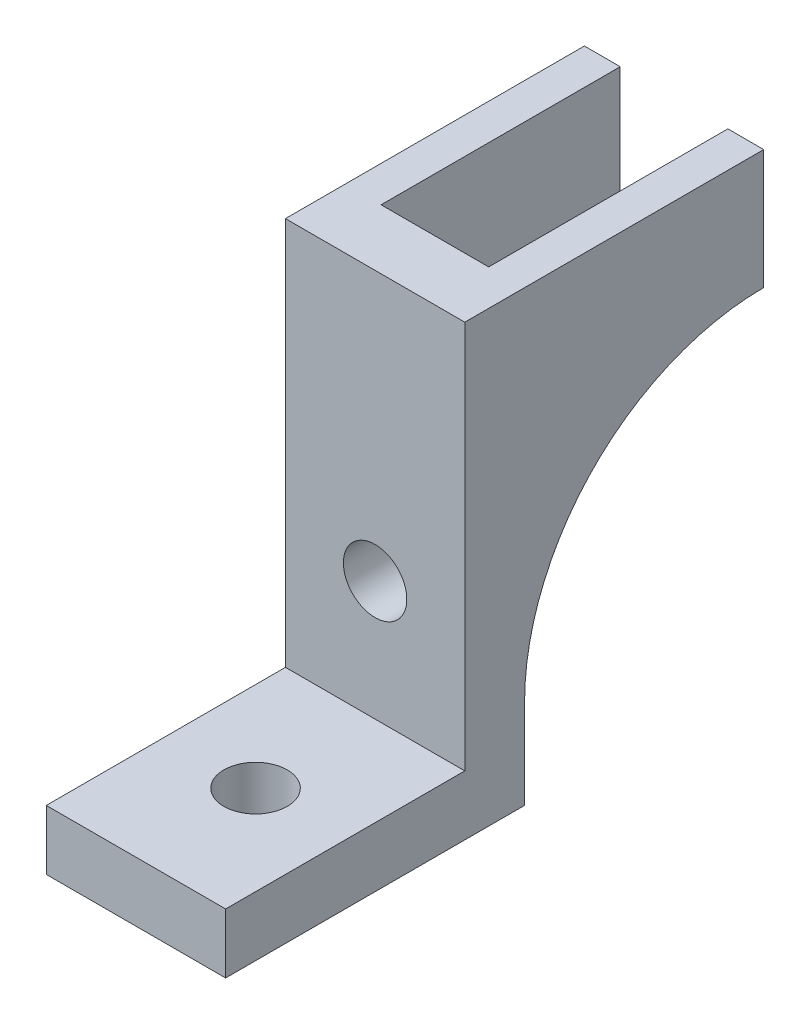
SolidWorks part; units mm, degrees
ref_plane "Front Plane" through (0, 0, 0) normal (0, 0, 1) x (1, 0, 0)
ref_plane "Top Plane" through (0, 0, 0) normal (0, 1, 0) x (1, 0, 0)
ref_plane "Right Plane" through (0, 0, 0) normal (1, 0, 0) x (0, 0, -1)
sketch "Sketch2" plane through (0, 0, 0) normal (0, 0, 1) x (1, 0, 0)
  line L1 (0, 0) -> (15, 0)
  line L2 (0, 0) -> (0, 37.5)
  line L3 (0, 37.5) -> (15, 37.5)
  line L4 (15, 0) -> (15, 37.5)
  dimension "D1" = 37.5
  dimension "D2" = 15
extrude "Boss-Extrude1" add sketch "Sketch2" along normal blind 5
sketch "Sketch3" plane through (0, 0, 5) normal (0, 0, 1) x (1, 0, 0)
  line L0 (15, 0) -> (15, 37.5) construction
  line L1 (0, 0) -> (15, 0)
  line L2 (0, 0) -> (0, 5)
  line L3 (0, 5) -> (15, 5)
  line L4 (15, 0) -> (15, 5)
  dimension "D1" = 5
extrude "Boss-Extrude2" add sketch "Sketch3" along normal blind 20
sketch "Sketch4" plane through (0, 0, 0) normal (0, 0, -1) x (-1, 0, 0)
  line L1 (-15, 37.5) -> (-12, 37.5)
  line L2 (-15, 37.5) -> (-15, 27.5)
  line L3 (-15, 27.5) -> (-12, 27.5)
  line L4 (-12, 37.5) -> (-12, 27.5)
  line L5 (0, 37.5) -> (-3, 37.5)
  line L6 (0, 37.5) -> (0, 27.5)
  line L7 (0, 27.5) -> (-3, 27.5)
  line L8 (-3, 37.5) -> (-3, 27.5)
  dimension "D1" = 3
  dimension "D2" = 3
  dimension "D3" = 10
  dimension "D4" = 10
extrude "Boss-Extrude3" add sketch "Sketch4" along normal blind 20
fillet "Fillet1" radius 20 2 edges at (1.5, 27.5, 0) (13.5, 27.5, 0)
sketch "Sketch6" plane through (0, 0, 0) normal (0, -1, 0) x (1, 0, 0)
  line L0 (0, 25) -> (15, 25) construction
  line L1 (0, 25) -> (0, 0) construction
  circle A0 centre (7.5, 15) radius 2.65
  dimension "D1" = 5.3
  dimension "D2" = 10
  dimension "D3" = 7.5
extrude "Cut-Extrude2" cut sketch "Sketch6" against normal blind 10
sketch "Sketch7" plane through (0, 0, 0) normal (0, 0, -1) x (-1, 0, 0)
  line L0 (0, 0) -> (-15, 0) construction
  line L1 (0, 7.5) -> (0, 0) construction
  circle A0 centre (-7.5, 15) radius 2.65
  dimension "D1" = 5.3
  dimension "D2" = 15
  dimension "D3" = 7.5
extrude "Cut-Extrude3" cut sketch "Sketch7" against normal blind 10
